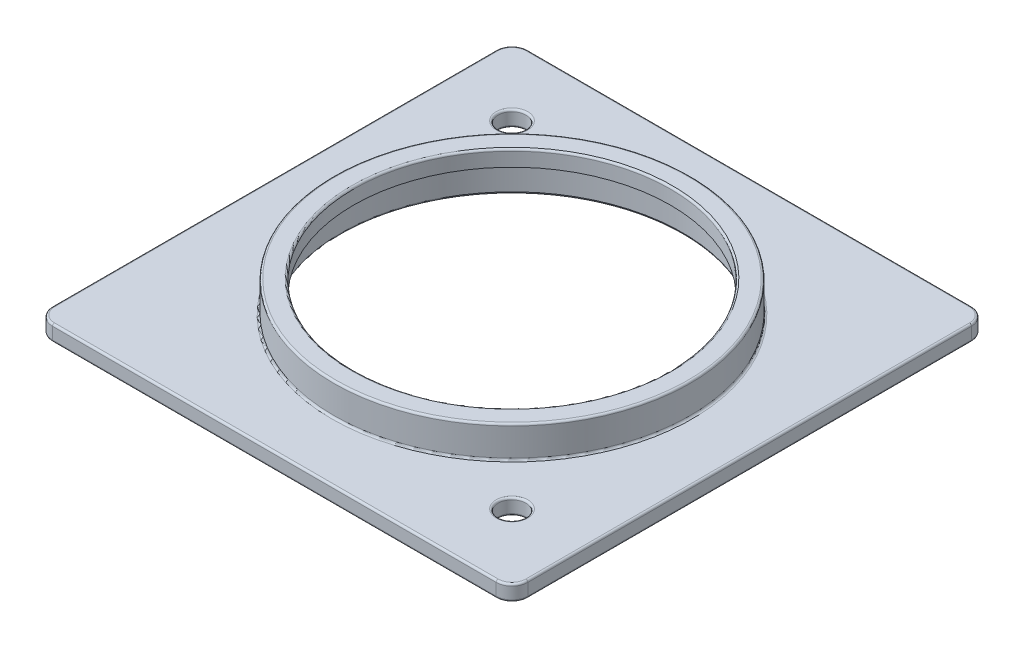
SolidWorks part; units mm, degrees
ref_plane "Front Plane" through (0, 0, 0) normal (0, 0, 1) x (1, 0, 0)
ref_plane "Top Plane" through (0, 0, 0) normal (0, 1, 0) x (1, 0, 0)
ref_plane "Right Plane" through (0, 0, 0) normal (1, 0, 0) x (0, 0, -1)
sketch "Sketch1" plane through (0, 0, 0) normal (0, 1, 0) x (1, 0, 0)
  line L0 (0, 0) -> (-21.2132, 21.2132) construction
  line L1 (0, 0) -> (21.2132, -21.2132) construction
  line L2 (0, 0) -> (-20, 0) construction
  line L4 (-30, -30) -> (30, -30)
  line L5 (-30, -30) -> (-30, 30)
  line L6 (-30, 30) -> (30, 30)
  line L7 (30, -30) -> (30, 30)
  line L8 (-30, -30) -> (30, 30) construction
  line L9 (-30, 30) -> (30, -30) construction
  circle A1 centre (0, 0) radius 20
  circle A2 centre (-21.2132, 21.2132) radius 1.75
  circle A3 centre (21.2132, -21.2132) radius 1.75
  circle A4 centre (0, 0) radius 21.5
  circle A5 centre (0, 0) radius 22.5
  dimension "D1" = 40
  dimension "D3" = 3.5
  dimension "D5" = 43
  dimension "D7" = 45
  dimension "D2" = 30
  dimension "D4" = 45
  dimension "D6" = 60
extrude "Boss-Extrude1" add sketch "Sketch1" along normal blind 2 contours L4 L7 L6 L5 A5 A3 A2 region at (-29.1515, 0, 0)
extrude "Boss-Extrude2" add sketch "Sketch1<2>" along normal blind 6 contours A4 | A5 A4 region at (-20.8919, 0, 0) region at (-21.8636, 0, 0)
sketch "Sketch1<2>" plane through (0, 0, 0) normal (0, 1, 0) x (1, 0, 0) same geometry as "Sketch1"
extrude "Cut-Extrude1" cut sketch "Sketch1<4>" along normal blind 4 contours A4 region at (-20.8919, 0, 0)
sketch "Sketch1<4>" plane through (0, 0, 0) normal (0, 1, 0) x (1, 0, 0) same geometry as "Sketch1"
fillet "Fillet1" radius 0.25 16 edges at (30, 0, 0) (0, 0, -30) (-30, 0, 0) (0, 0, 30) (-21.2132, 0, -19.4632) (21.2132, 0, 22.9632) (0, 0, 21.5) (-30, 2, 0) (0, 2, -30) (30, 2, 0) (0, 2, 30) (-21.2132, 2, -19.4632) (21.2132, 2, 22.9632) (0, 2, 22.5) (0, 6, 22.5) (0, 6, 20)
fillet "Fillet2" radius 2 12 edges at (-29.9268, 0.0732, 29.9268) (-29.9268, 1.9268, 29.9268) (-29.9268, 0.0732, -29.9268) (-29.9268, 1.9268, -29.9268) (29.9268, 0.0732, -29.9268) (29.9268, 1.9268, -29.9268) (29.9268, 0.0732, 29.9268) (29.9268, 1.9268, 29.9268) (30, 1, 30) (30, 1, -30) (-30, 1, -30) (-30, 1, 30)
